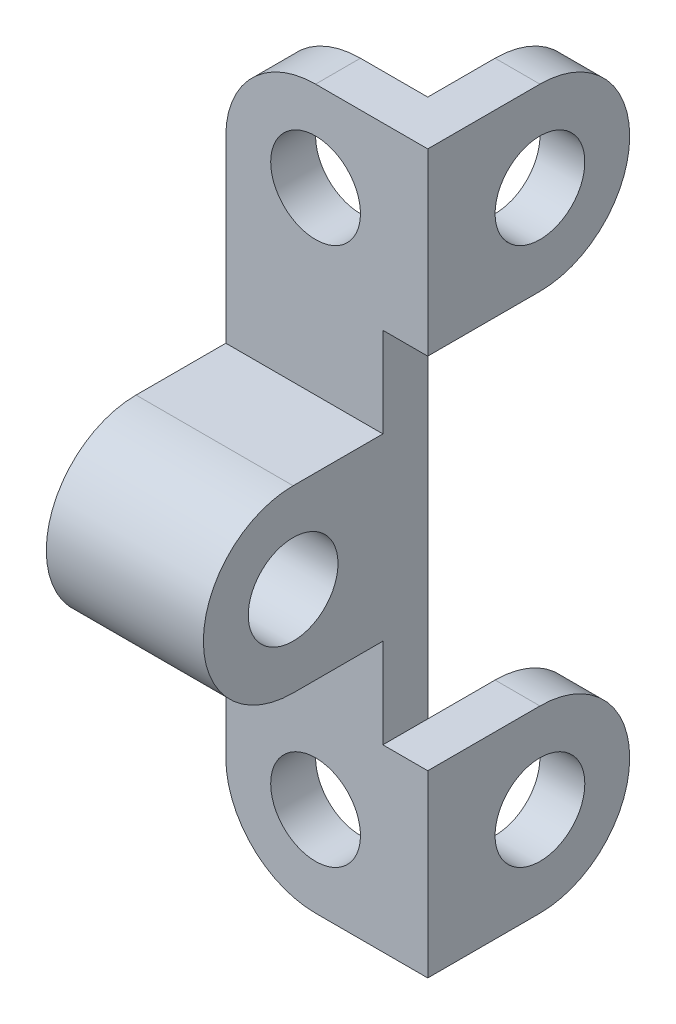
SolidWorks part; units mm, degrees
ref_plane "Front Plane" through (0, 0, 0) normal (1, 0, 0) x (0, 1, 0)
ref_plane "Top Plane" through (0, 0, 0) normal (0, 0, 1) x (0, 1, 0)
ref_plane "Right Plane" through (0, 0, 0) normal (0, 1, 0) x (-1, 0, 0)
sketch "Sketch1" plane through (0, 0, 0) normal (1, 0, 0) x (0, 1, 0)
  line L0 (-20, 0) -> (-20, -20)
  line L1 (-20, -20) -> (20, -20)
  line L2 (20, -20) -> (20, 0)
  line L3 (-80, -20) -> (80, -20)
  line L4 (-80, -20) -> (-80, -30)
  line L5 (-80, -30) -> (80, -30)
  line L6 (80, -30) -> (80, -20)
  arc A0 (20, 0) -> (-20, 0) centre (0, 0) ccw
  circle A1 centre (0, 0) radius 10
  point P11 (0, -30)
  dimension "D1" = 40
  dimension "D2" = 20
  dimension "D3" = 160
  dimension "D4" = 10
extrude "Boss-Extrude1" add sketch "Sketch1" against normal blind 20 contours L5 L6 L3 L1 L4 region at (0, 0, -25)
extrude "Boss-Extrude2" add sketch "Sketch1<3>" along normal blind 15 contours L5 L6 L3 L1 L4 region at (0, 0, -25)
sketch "Sketch1<3>" plane through (0, 0, 0) normal (1, 0, 0) x (0, 1, 0) same geometry as "Sketch1"
extrude "Boss-Extrude3" add sketch "Sketch1<4>" along normal blind 15 contours L2 A0 L0 L1 A1 region at (0, 0, 19.4343)
sketch "Sketch1<4>" plane through (0, 0, 0) normal (1, 0, 0) x (0, 1, 0) same geometry as "Sketch1"
extrude "Boss-Extrude4" add sketch "Sketch1<5>" against normal blind 20 contours L2 A0 L0 L1 A1 region at (0, 0, 19.4343)
sketch "Sketch1<5>" plane through (0, 0, 0) normal (1, 0, 0) x (0, 1, 0) same geometry as "Sketch1"
fillet "Fillet1" radius 20 2 edges at (-20, 80, -25) (-20, -80, -25)
sketch "Sketch2" plane through (15, 0, 0) normal (1, 0, 0) x (0, 1, 0)
  line L0 (-80, -30) -> (80, -30) construction
  line L1 (-80, -20) -> (-40, -20)
  line L2 (-80, -20) -> (-80, -30)
  line L3 (-80, -30) -> (-40, -30)
  line L4 (-40, -20) -> (-40, -30)
  line L5 (0, 0) -> (0, -43.57) construction
  line L6 (80, -30) -> (40, -30)
  line L7 (40, -20) -> (40, -30)
  line L8 (80, -20) -> (40, -20)
  line L9 (80, -20) -> (80, -30)
  dimension "D1" = 40
extrude "Boss-Extrude5" add sketch "Sketch2" along normal blind 10
sketch "Sketch3" plane through (25, 0, 0) normal (1, 0, 0) x (0, 1, 0)
  line L0 (-80, -20) -> (-40, -20)
  line L1 (-40, -20) -> (-40, -45)
  line L3 (-80, -45) -> (-80, -20)
  line L4 (0, 0) -> (0, -18.0386) construction
  line L5 (80, -45) -> (80, -20)
  line L6 (80, -20) -> (40, -20)
  line L7 (40, -20) -> (40, -45)
  arc A0 (-80, -45) -> (-40, -45) centre (-60, -45) ccw
  circle A1 centre (-60, -45) radius 10
  circle A2 centre (60, -45) radius 10
  arc A3 (80, -45) -> (40, -45) centre (60, -45) cw
  dimension "D3" = 40
  dimension "D2" = 20
  dimension "D1" = 25
extrude "Boss-Extrude6" add sketch "Sketch3" against normal blind 10
sketch "Sketch4" plane through (0, 0, 0) normal (0, 0, 1) x (0, 1, 0)
  line L0 (0, 0) -> (0, -26.7307) construction
  circle A0 centre (-60, 0) radius 10
  arc A1 (-60, 20) -> (-80, 0) centre (-60, 0) ccw construction
  circle A2 centre (60, 0) radius 10
  dimension "D1" = 20
extrude "Cut-Extrude1" cut sketch "Sketch4" against normal through all both and the other way through all
